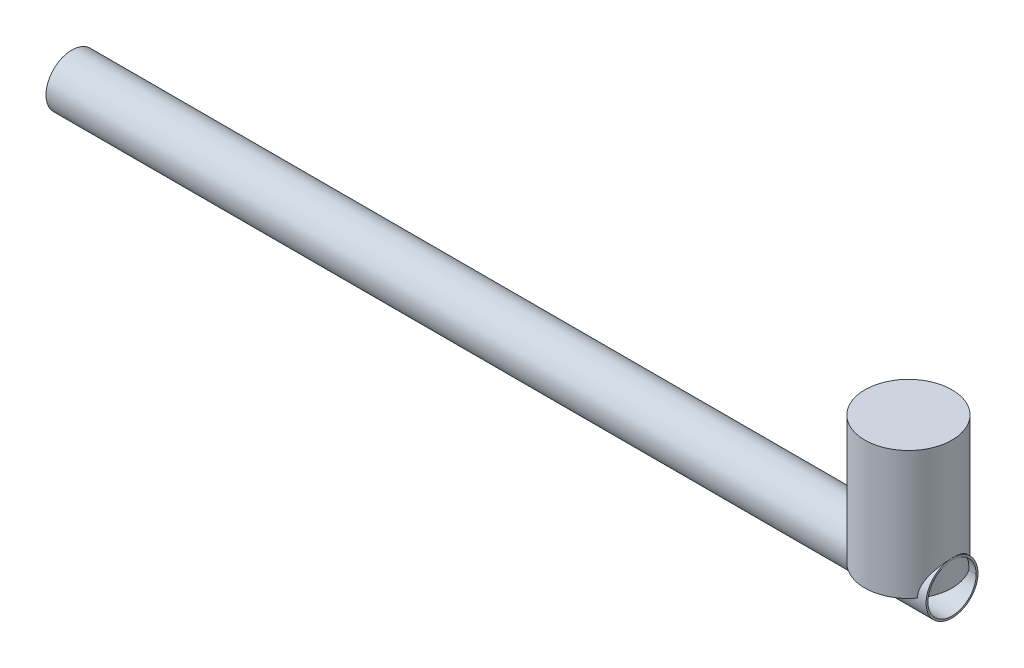
SolidWorks part; units mm, degrees
ref_plane "Front Plane" through (0, 0, 0) normal (0, 0, 1) x (1, 0, 0)
ref_plane "Top Plane" through (0, 0, 0) normal (0, 1, 0) x (1, 0, 0)
ref_plane "Right Plane" through (0, 0, 0) normal (1, 0, 0) x (0, 0, -1)
sketch "Sketch1" plane through (0, 0, 0) normal (1, 0, 0) x (0, 0, -1)
  circle A0 centre (0, 0) radius 12.7
  circle A1 centre (0, 0) radius 11.811
extrude "Boss-Extrude1" add sketch "Sketch1" along normal blind 430.586
sketch "Sketch2" plane through (0, 0, 0) normal (0, 1, 0) x (1, 0, 0)
  circle A0 centre (409.2547, 0) radius 21.3313
extrude "Boss-Extrude2" add sketch "Sketch2" along normal blind 62.7
